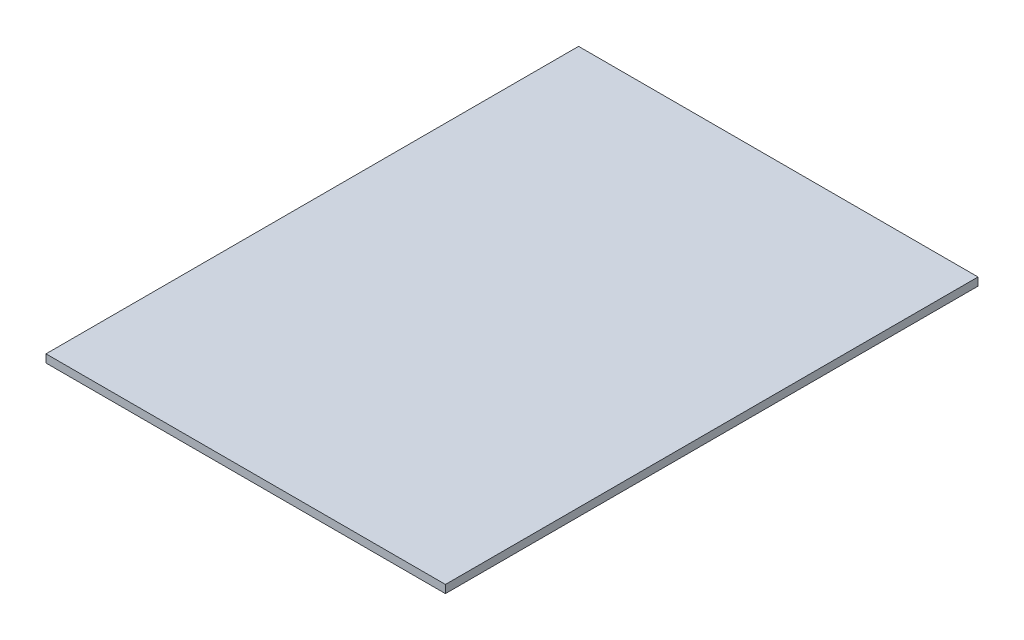
SolidWorks part; units mm, degrees
ref_plane "Front Plane" through (0, 0, 0) normal (0, 0, 1) x (1, 0, 0)
ref_plane "Top Plane" through (0, 0, 0) normal (0, 1, 0) x (1, 0, 0)
ref_plane "Right Plane" through (0, 0, 0) normal (1, 0, 0) x (0, 0, -1)
sketch "Sketch1" plane through (0, 0, 0) normal (0, 1, 0) x (1, 0, 0)
  line L1 (-75, -100) -> (75, -100)
  line L2 (-75, -100) -> (-75, 100)
  line L3 (-75, 100) -> (75, 100)
  line L4 (75, -100) -> (75, 100)
  line L5 (-75, -100) -> (75, 100) construction
  line L6 (-75, 100) -> (75, -100) construction
  point P0 (0, 0)
  dimension "D1" = 150
  dimension "D2" = 200
extrude "Boss-Extrude1" add sketch "Sketch1" along normal blind 3
